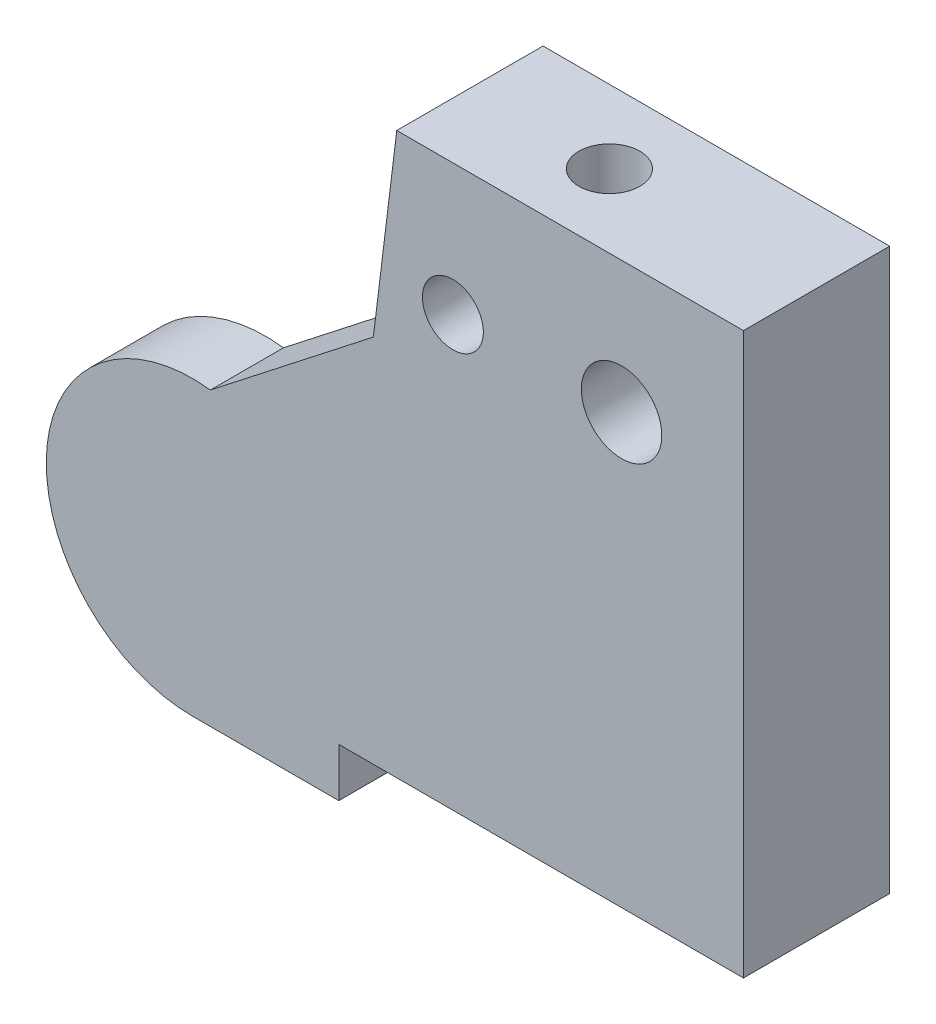
SolidWorks part; units mm, degrees
note: The reader was unsure of these and kept them because the rebuilt part matched: shared geometry of "Esboço1<3>".
ref_plane "Plano frontal" through (0, 0, 0) normal (0, 0, 1) x (1, 0, 0)
ref_plane "Plano superior" through (0, 0, 0) normal (0, 1, 0) x (1, 0, 0)
ref_plane "Plano direito" through (0, 0, 0) normal (1, 0, 0) x (0, 0, -1)
sketch "Esboço1" plane through (0, 0, 0) normal (0, 0, 1) x (1, 0, 0)
  line L0 (0, 0) -> (0, -2)
  line L1 (0, 0) -> (16.6, 0)
  line L2 (0, 0) -> (0, 23)
  line L3 (0, 23) -> (16.6, 23) construction
  line L4 (16.6, 0) -> (16.6, 23) construction
  line L5 (0, -2) -> (-6, -2)
  line L6 (-6, -2) -> (-6, 4) construction
  line L7 (-6, 10) -> (0, 10) construction
  line L8 (0, 10) -> (0, 16) construction
  line L13 (0, 23) -> (16.6, 23)
  line L14 (16.6, 0) -> (16.6, 23)
  line L15 (11.6, 23) -> (11.6, 17.6) construction
  circle A0 centre (-6, 4) radius 6 construction
  arc A1 (-6, -2) -> (-6, 10) centre (-6, 4) cw
  arc A2 (-6, 10) -> (0, 16) centre (-6, 16) ccw
  circle A6 centre (11.6, 17.6) radius 1.5
  circle A7 centre (4.68, 17.61) radius 0.5
  dimension "D13" = 3
  dimension "D17" = 1
  dimension "D1" = 16.6
  dimension "D2" = 23
  dimension "D3" = 6
  dimension "D4" = 2
  dimension "D5" = 6
  dimension "D6" = 6
  dimension "D12" = 5.4
  dimension "D14" = 5
  dimension "D15" = 4.68
  dimension "D16" = 5.39
extrude "Ressalto-extrusão1" add sketch "Esboço1" along normal blind 3 contours A2 A1 L5 L0 L2
extrude "Ressalto-extrusão2" add sketch "Esboço1<3>" along normal blind 6
sketch "Esboço1<3>" plane through (0, 0, 0) normal (0, 0, 1) x (1, 0, 0) same geometry as "Esboço1"
mirror "Espelhar1" about plane through (0, 0, 6) normal (0, 0, 1) of bodies 102 104
delete or keep bodies "Corpo-Excluir1" type delete bodies bodies 102
sketch "Esboço3" plane through (0, 0, 12) normal (0, 0, 1) x (1, 0, 0)
  line L0 (0.8389, 15.2818) -> (5.87, 17.6097) construction
  line L1 (0, 23) -> (16.6, 23) construction
  line L2 (5.87, 17.6097) -> (7.85, 23) construction
  line L3 (5.87, 17.6097) -> (0, 17.6097) construction
  line L4 (0, 16) -> (0, 23) construction
  line L5 (0, 23) -> (16.6, 23) construction
  circle A0 centre (4.68, 17.61) radius 0.5 construction
  circle A1 centre (4.68, 17.61) radius 0.5
  circle A2 centre (4.6762, 18.7101) radius 1.5
  dimension "D4" = 3
  dimension "D1" = 24.83
  dimension "D2" = 135
  dimension "D3" = 5.87
sketch "Esboço4" plane through (0, 0, 6) normal (0, 0, -1) x (-1, 0, 0)
  line L0 (0.0447, 3.2688) -> (-2.378, 23) construction
  line L1 (0, 0) -> (0, 23) construction
  line L2 (0, 23) -> (-16.6, 23) construction
  line L3 (0, 23) -> (-16.6, 23) construction
  line L4 (0, 3.633) -> (-2.378, 23)
  line L5 (-2.378, 23) -> (0, 23)
  line L6 (0, 23) -> (0, 3.633)
  arc A0 (6, -2) -> (6, 10) centre (6, 4) ccw construction
  arc A1 (6, -2) -> (6, 10) centre (6, 4) ccw construction
  circle A2 centre (6, 4) radius 6 construction
  dimension "D1" = 7
extrude "Corte-extrusão1" cut sketch "Esboço4" against normal blind 3
sketch "Esboço5" plane through (0, 0, 9) normal (0, 0, -1) x (-1, 0, 0)
  line L0 (5.2688, 9.9553) -> (-0.6865, 9.2241)
  line L1 (-2.378, 23) -> (0, 3.633) construction
  line L2 (-0.6865, 9.2241) -> (-2.378, 23)
  line L8 (0, 16) -> (0, 23)
  line L9 (0, 23) -> (-2.378, 23)
  line L10 (-2.378, 23) -> (0, 3.633)
  line L11 (0, 3.633) -> (0, 0)
  line L12 (0, 0) -> (0, -2)
  line L13 (0, -2) -> (6, -2)
  line L14 (0, 16) -> (0, 23)
  line L15 (0, 23) -> (-2.378, 23)
  line L16 (-2.378, 23) -> (0, 3.633)
  line L17 (0, 3.633) -> (0, 0)
  line L18 (0, 0) -> (0, -2)
  line L19 (0, -2) -> (6, -2)
  arc A0 (6, -2) -> (6, 10) centre (6, 4) ccw construction
  arc A1 (6, -2) -> (6, 10) centre (6, 4) ccw
  circle A2 centre (6, 4) radius 6
  arc A5 (0, 16) -> (6, 10) centre (6, 16) ccw
  arc A6 (6, -2) -> (6, 10) centre (6, 4) ccw
  arc A7 (0, 16) -> (6, 10) centre (6, 16) ccw
  arc A8 (6, -2) -> (6, 10) centre (6, 4) ccw
  arc M9 (6, 10) -> (0, 16) centre (6, 16) cw
  line M10 (0, 16) -> (0, 23)
  line M11 (0, 23) -> (-2.378, 23)
  line M12 (-2.378, 23) -> (0, 3.633)
  dimension "D1" = 0
extrude "Corte-extrusão2" cut sketch "Esboço5" against normal blind 3 contours A2 L0 M9 M10 M11 M12
chamfer "Chanfro1" distance 6 angle 45 3 edges at (-2.2911, 9.5897, 9) (0.6865, 9.2241, 10.5) (-2.2911, 9.5897, 12)
sketch "Esboço6" plane through (0, 0, 0) normal (0, -1, 0) x (1, 0, 0)
  line L0 (16.6, 9) -> (0, 9) construction
  line L1 (16.6, 6) -> (16.6, 12) construction
  point P5 (4, 9)
  point P6 (12.6, 9)
  dimension "D1" = 4
  dimension "D2" = 4
hole_wizard "Furo roscado de M3x0.51" positions "Esboço8" profile "Esboço7" tap size "M3x0.5" standard "Ansi Metric"
sketch "Esboço8" plane through (0, 0, 0) normal (0, -1, 0) x (1, 0, 0)
  point P0 (4, 9)
  point P3 (12.6, 9)
sketch "Esboço7" plane through (4, 0, 9) normal (1, 0, 0) x (0, 0, -1)
  line L0 (0, 0) -> (0, 9.2511)
  line L1 (0, 9.2511) -> (1.25, 8.5)
  line L2 (1.25, 8.5) -> (1.25, 0)
  line L5 (1.25, 0) -> (0, 0)
  line L10 (0, 9.2511) -> (-1.25, 8.5) construction
  line L11 (0, -6.35) -> (0, 107.95) construction
  dimension "Tap Drill Dia." = 2.5
  dimension "Tap Drill Depth" = 8.5
  dimension "Drill Angle" = 118
hole_wizard "Furo roscado de M3x0.52" positions "Esboço13" profile "Esboço12" tap size "M3x0.5" standard "Ansi Metric"
sketch "Esboço13" plane through (0, 0, 6) normal (0, 0, -1) x (-1, 0, 0)
  point P0 (-4.68, 17.61)
sketch "Esboço12" plane through (4.68, 17.61, 6) normal (1, 0, 0) x (0, 1, 0)
  line L0 (0, 0) -> (0, 6.7501)
  line L1 (0, 6.7501) -> (1.25, 5.999)
  line L2 (1.25, 5.999) -> (1.25, 0)
  line L5 (1.25, 0) -> (0, 0)
  line L10 (0, 6.7501) -> (-1.25, 5.999) construction
  line L11 (0, -6.35) -> (0, 107.95) construction
  dimension "Tap Drill Dia." = 2.5
  dimension "Tap Drill Depth" = 5.999
  dimension "Drill Angle" = 118
cosmetic thread "Rosca de furo1" parameters "D1"=6, "D2"=3
sketch "Esboço14" plane through (0, 23, 0) normal (0, 1, 0) x (-1, 0, 0)
  line L0 (-16.6, 9) -> (-2.378, 9) construction
  line L1 (-16.6, 6) -> (-16.6, 12) construction
  line L2 (-2.378, 12) -> (-2.378, 6) construction
  point P6 (-8.1, 9)
  dimension "D1" = 8.5
hole_wizard "Furo roscado de M3x0.53" positions "Esboço16" profile "Esboço15" tap size "M3x0.5" standard "Ansi Metric"
sketch "Esboço16" plane through (0, 23, 0) normal (0, 1, 0) x (-1, 0, 0)
  point P0 (-8.1, 9)
cosmetic thread "Rosca de furo2" parameters "D1"=3, "D2"=3
sketch "Esboço15" plane through (8.1, 23, 9) normal (1, 0, 0) x (0, 0, 1)
  line L0 (0, 0) -> (0, 3.7511)
  line L1 (0, 3.7511) -> (1.25, 3)
  line L2 (1.25, 3) -> (1.25, 0)
  line L5 (1.25, 0) -> (0, 0)
  line L10 (0, 3.7511) -> (-1.25, 3) construction
  line L11 (0, -6.35) -> (0, 107.95) construction
  dimension "Tap Drill Dia." = 2.5
  dimension "Tap Drill Depth" = 3
  dimension "Drill Angle" = 118
sketch "Esboço17" plane through (0, 0, 9) normal (0, 0, -1) x (-1, 0, 0)
  arc A0 (6, -2) -> (5.2688, 9.9553) centre (6, 4) ccw construction
  arc A1 (6, -2) -> (5.2688, 9.9553) centre (6, 4) ccw construction
  circle A2 centre (6, 4) radius 2.45
  dimension "D1" = 4.9
extrude "Ressalto-extrusão3" add sketch "Esboço17" along normal blind 3.5
chamfer "Chanfro2" distance 0.5 angle 45 1 edges at (-8.45, 4, 5.5)
hole_wizard "Furo roscado de M4x0.73" positions "Esboço21" profile "Esboço20" tap size "M4x0.7" standard "Ansi Metric"
sketch "Esboço21" plane through (0, 0, 6) normal (0, 0, -1) x (-1, 0, 0)
  point P0 (-11.6, 17.6)
sketch "Esboço20" plane through (11.6, 17.6, 6) normal (1, 0, 0) x (0, 1, 0)
  line L0 (0, 0) -> (0, 12.4914)
  line L1 (0, 12.4914) -> (1.65, 11.5)
  line L2 (1.65, 11.5) -> (1.65, 0)
  line L5 (1.65, 0) -> (0, 0)
  line L10 (0, 12.4914) -> (-1.65, 11.5) construction
  line L11 (0, -6.35) -> (0, 107.95) construction
  dimension "Tap Drill Dia." = 3.3
  dimension "Tap Drill Depth" = 11.5
  dimension "Drill Angle" = 118
cosmetic thread "Rosca de furo3" parameters "D1"=6, "D2"=4
